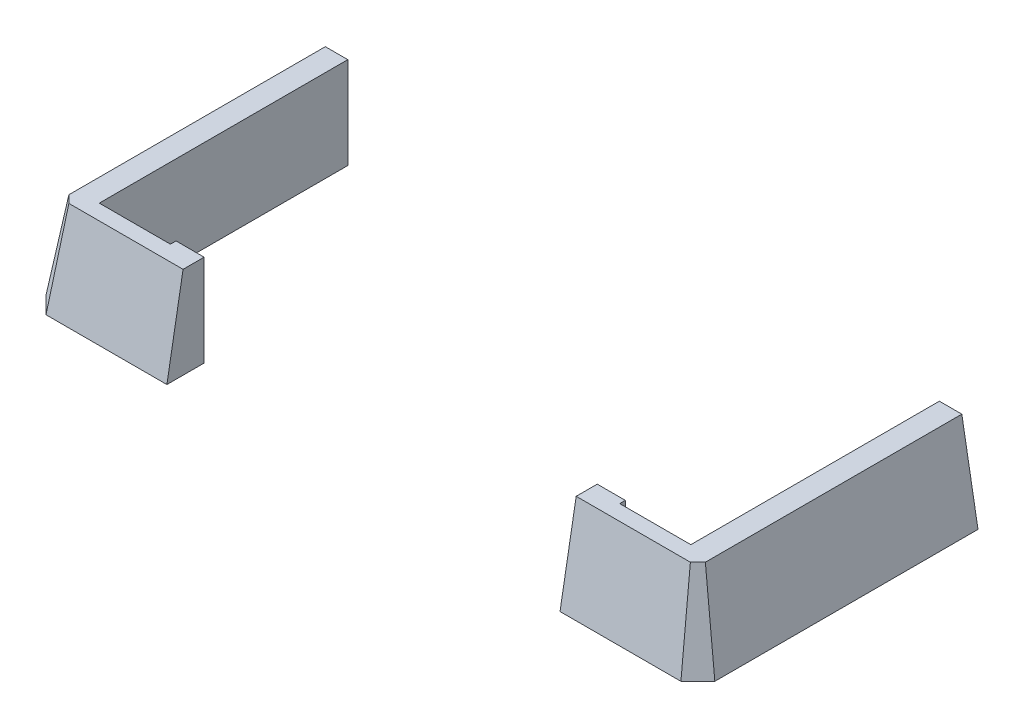
SolidWorks part; units mm, degrees
ref_plane "Front Plane" through (0, 0, 0) normal (0, 0, 1) x (1, 0, 0)
ref_plane "Top Plane" through (0, 0, 0) normal (0, 1, 0) x (1, 0, 0)
ref_plane "Right Plane" through (0, 0, 0) normal (1, 0, 0) x (0, 0, -1)
sketch "Sketch1" plane through (0, 0, 0) normal (0, 1, 0) x (1, 0, 0)
  line L9 (0, 0) -> (-158, 0) construction
  line L10 (0, 0) -> (0, 76.9384) construction
  line L11 (0, 0) -> (-158, 0) construction
  line L12 (-158, 99.7575) -> (-158, -30.0025) construction
  line L14 (-158, 99.7575) -> (-170, 99.7575) construction
  line L16 (-170, 99.7575) -> (-170, -41.2425) construction
  line L17 (-170, -41.2425) -> (-158, -41.2425) construction
  line L19 (-158, -30.0025) -> (-105, -30.0025) construction
  line L20 (-105, -30.0025) -> (-105, -41.2425) construction
  line L21 (-105, -41.2425) -> (-158, -41.2425) construction
  line L22 (-158, -30.0025) -> (-158, -41.2425) construction
  dimension "D5" = 158
  dimension "D6" = 12
  dimension "D7" = 53
  dimension "D8" = 11.24
  dimension "D9" = 41.2425
  dimension "D10" = 141
ref_plane "Plane1" through (0, -25, 0) normal (0, 1, 0) x (1, 0, 0)
ref_plane "Plane2" through (0, 24, 0) normal (0, 1, 0) x (1, 0, 0)
sketch "Sketch3" plane through (0, 24, 0) normal (0, 1, 0) x (1, 0, 0)
  line L0 (-170, 99.7575) -> (-158, 99.7575)
  line L1 (-158, 99.7575) -> (-158, -30.0025)
  line L3 (-105, -30.0025) -> (-105, -41.2425)
  line L4 (-105, -41.2425) -> (-166, -41.2425)
  line L5 (-170, -37.2425) -> (-170, 99.7575)
  line L6 (-166, -41.2425) -> (-170, -37.2425)
  line L7 (-105, -30.0025) -> (-120, -30)
  line L8 (-120, -30) -> (-120, -33.0025)
  line L9 (-120, -33.0025) -> (-158, -33.0025)
  line L10 (-158, -33.0025) -> (-158, -30.0025)
  point P11 (-170, -41.2425)
  dimension "D1" = 3
extrude "Boss-Extrude1" add sketch "Sketch3" against normal up to surface (49 mm away) up to plane "Plane1"
draft "Draft1" type of draft neutral plane draft angle 10 faces to draft 3 face at (-135.5, -0.5, 41.2425) face at (-168, -0.5, 39.2425) face at (-170, -0.5, -31.2575) neutral plane through (0, 24, 0) neutral plane normal (0, 1, 0) parameters "D1"=10
mirror "Mirror2" about plane through (0, 0, 0) normal (1, 0, 0) of bodies 105
